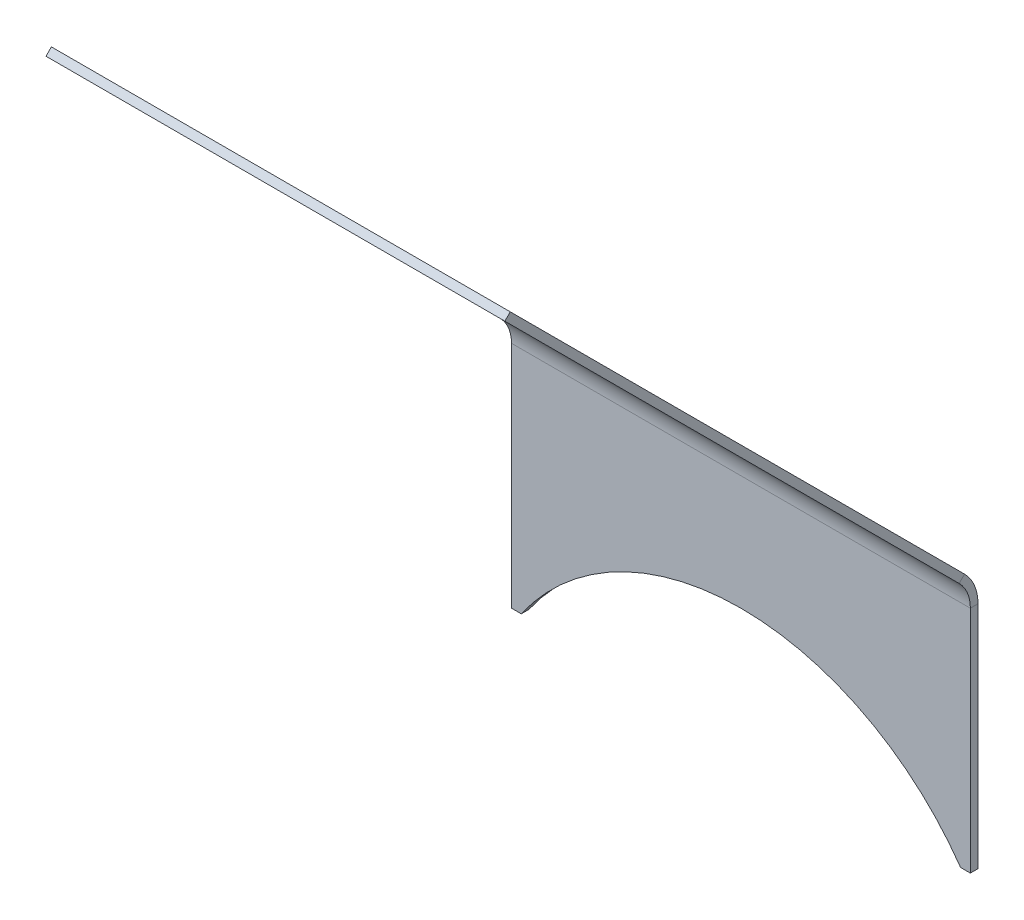
SolidWorks part; units mm, degrees
note: The reader was unsure of these and kept them because the rebuilt part matched: flange length of "Ребро-кромка1".
material "AISI 304"
ref_plane "Спереди" through (0, 0, 0) normal (0, 0, 1) x (1, 0, 0)
ref_plane "Сверху" through (0, 0, 0) normal (0, 1, 0) x (1, 0, 0)
ref_plane "Справа" through (0, 0, 0) normal (1, 0, 0) x (0, 0, -1)
sketch "Эскиз2" plane through (0, 0, 0) normal (0, 0, 1) x (1, 0, 0)
  line L5 (0, 0) -> (120, 0)
  line L6 (120, 0) -> (120, 60)
  line L8 (0, 60) -> (0, 0)
  line L9 (120, 60) -> (0, 60)
  line L10 (60, 60) -> (60, 0) construction
  dimension "D2" = 60
  dimension "D3" = 120
sketch "Эскиз3" plane through (0, 0, 0) normal (0, 0, 1) x (1, 0, 0)
  line L0 (50, 0) -> (-50, 0) construction
  line L1 (0, -50) -> (0, 50) construction
  circle A0 centre (60, -40) radius 70
  dimension "D1" = 140
  dimension "D2" = 40
  dimension "D3" = 60
base flange "Базовая кромка1" sketch "Эскиз2" thickness 2 reverse thickness direction yes parameters "D1"=10
edge flange "Ребро-кромка1" sketch "Эскиз10" flange angle 135 flange length 173 flange position bend outside bend radius 10 thickness 2 relief rectangular parameters "D6"=10
sketch "Эскиз10" plane through (0, 60, 2) normal (0, 0.7071, -0.7071) x (-1, 0, 0)
  line L0 (-120, 0) -> (0, 0) construction
  line L1 (-120, 0) -> (0, 0)
  line L2 (-120, 0) -> (-120, 172.1716)
  line L3 (-120, 172.1716) -> (0, 172.1716)
  line L4 (0, 172.1716) -> (0, 0)
bend "EdgeBend1" bend radius 10 bend angle 45 parameters "D5"=1
extrude "Вырез-Вытянуть3" cut sketch "Эскиз3" along normal up to next contours A0 normal cut yes
sketch "Сгиб-Линии1" plane through (0, 0, 0) normal (0, 1, 0) x (1, 0, 0)
sketch "Граничная рамка1" plane through (0, 0, 0) normal (0, 1, 0) x (1, 0, 0)
sheet metal parameters "Листовой металл7" thickness 2 parameters "D1"=10
flat pattern "Развертка7" [suppressed]
sketch "Сгиб-Линии2" plane through (0, 0, 0) normal (0, 1, 0) x (1, 0, 0)
sketch "Граничная рамка2" [suppressed] plane through (0, 0, 0) normal (0, 1, 0) x (1, 0, 0)
sheet metal parameters "Листовой металл8" thickness 2 parameters "D1"=10
flat pattern "Развертка7" [suppressed]
sketch "Сгиб-Линии2" plane through (0, 0, 0) normal (0, 1, 0) x (1, 0, 0)
sketch "Граничная рамка2" [suppressed] plane through (0, 0, 0) normal (0, 1, 0) x (1, 0, 0)
bend of the flat pattern "Плоское состояние-<EdgeBend1>1"
sheet metal parameters "Листовой металл9" thickness 2 parameters "D1"=10
flat pattern "Развертка7" [suppressed]
sketch "Сгиб-Линии2" plane through (0, 0, 0) normal (0, 1, 0) x (1, 0, 0)
sketch "Граничная рамка2" [suppressed] plane through (0, 0, 0) normal (0, 1, 0) x (1, 0, 0)
bend of the flat pattern "Плоское состояние-<EdgeBend1>1"
